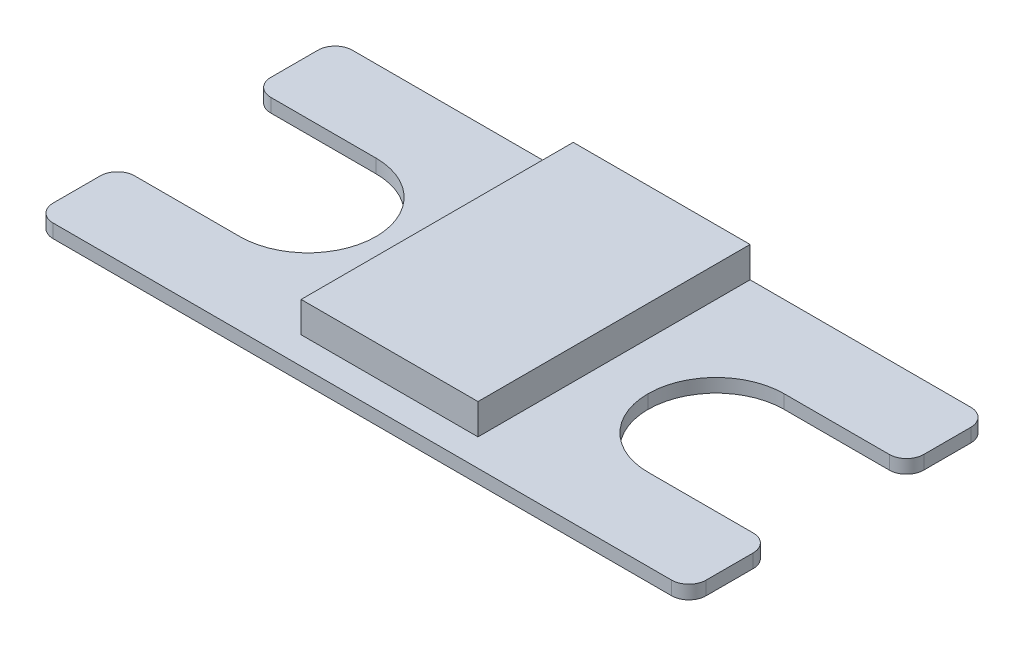
SolidWorks part; units mm, degrees
ref_plane "Front Plane" through (0, 0, 0) normal (0, 0, 1) x (1, 0, 0)
ref_plane "Top Plane" through (0, 0, 0) normal (0, 1, 0) x (1, 0, 0)
ref_plane "Right Plane" through (0, 0, 0) normal (1, 0, 0) x (0, 0, -1)
sketch "Sketch1" plane through (0, 0, 0) normal (0, 1, 0) x (1, 0, 0)
  line L0 (0, 0) -> (0, 6)
  line L1 (0, 6) -> (14, 6)
  line L2 (14, 6) -> (14, 16)
  line L3 (14, 16) -> (0, 16)
  line L4 (0, 16) -> (0, 22)
  line L5 (0, 22) -> (48, 22)
  line L6 (48, 22) -> (48, 16)
  line L7 (48, 16) -> (34, 16)
  line L8 (34, 16) -> (34, 6)
  line L9 (34, 6) -> (48, 6)
  line L10 (48, 6) -> (48, 0)
  line L11 (48, 0) -> (0, 0)
  dimension "D1" = 6
  dimension "D2" = 14
  dimension "D3" = 48
  dimension "D4" = 10
extrude "Boss-Extrude1" add sketch "Sketch1" along normal blind 1
fillet "Fillet1" radius 1.27 8 edges at (48, 0.5, 0) (48, 0.5, -6) (48, 0.5, -16) (48, 0.5, -22) (0, 0.5, -22) (0, 0.5, -16) (0, 0.5, -6) (0, 0.5, 0)
fillet "Fillet2" radius 5 4 edges at (34, 0.5, -6) (34, 0.5, -16) (14, 0.5, -6) (14, 0.5, -16)
sketch "Sketch2" plane through (0, 1, 0) normal (0, 1, 0) x (1, 0, 0)
  line L0 (46.73, 22) -> (1.27, 22) construction
  line L1 (17.5, 22) -> (30.5, 22)
  line L2 (17.5, 22) -> (17.5, 2)
  line L3 (17.5, 2) -> (30.5, 2)
  line L4 (30.5, 22) -> (30.5, 2)
  line L5 (1.27, 0) -> (46.73, 0) construction
  point P8 (24, 0)
  point P9 (24, 2)
  dimension "D1" = 13
  dimension "D2" = 20
extrude "Boss-Extrude2" add sketch "Sketch2" along normal blind 2.25
